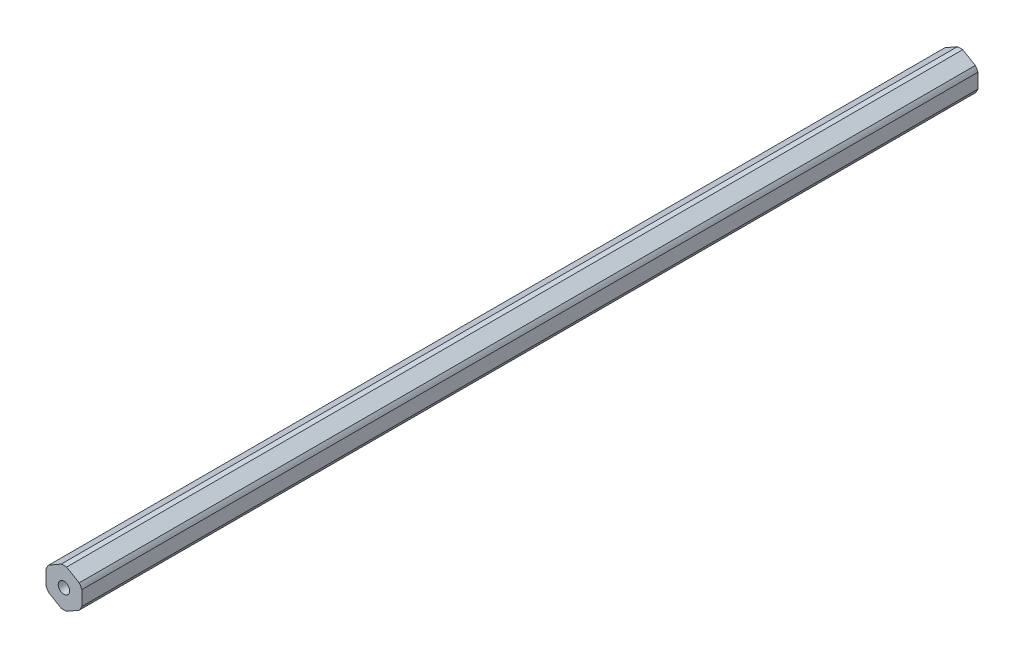
SolidWorks part; units mm, degrees
material "7075-T6 (SN)"
ref_plane "Front Plane" through (0, 0, 0) normal (0, 0, 1) x (1, 0, 0)
ref_plane "Top Plane" through (0, 0, 0) normal (0, 1, 0) x (1, 0, 0)
ref_plane "Right Plane" through (0, 0, 0) normal (1, 0, 0) x (0, 0, -1)
sketch "Sketch1" plane through (0, 0, 0) normal (0, 0, 1) x (1, 0, 0)
  line L7 (6.35, 3.6662) -> (0, 7.3323)
  line L8 (0, 7.3323) -> (-6.35, 3.6662)
  line L9 (-6.35, 3.6662) -> (-6.35, -3.6662)
  line L10 (-6.35, -3.6662) -> (0, -7.3323)
  line L11 (0, -7.3323) -> (6.35, -3.6662)
  line L12 (6.35, -3.6662) -> (6.35, 3.6662)
  circle A0 centre (0, 0) radius 6.35 construction
  circle A2 centre (0, 0) radius 6.858
  dimension "D1" = 12.7
  dimension "D2" = 13.716
extrude "Boss-Extrude1" add sketch "Sketch1" along normal mid plane 317.7032 contours L12 A2 L7 L8 L9 L10 L11 region at (0, 0, 0)
sketch "Sketch2" plane through (0, 0, 158.8516) normal (0, 0, 1) x (1, 0, 0)
  circle A0 centre (0, 0) radius 2.0193
  dimension "D1" = 4.0386
extrude "Cut-Extrude1" cut sketch "Sketch2" against normal through all
